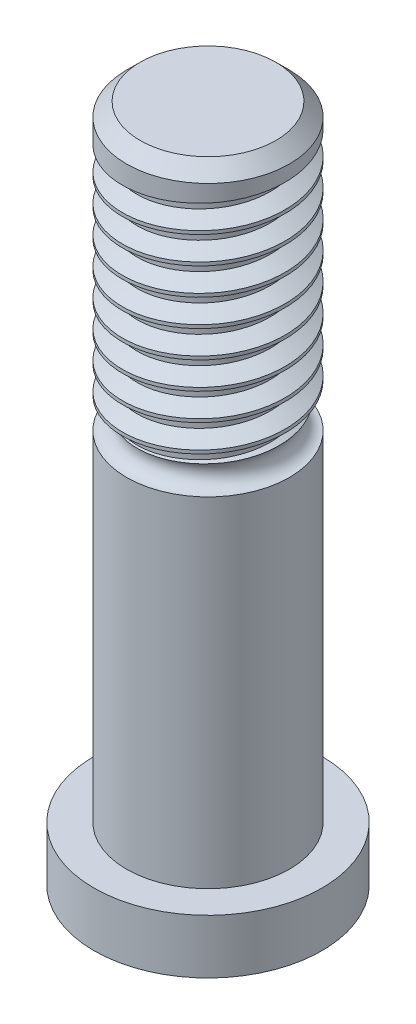
SolidWorks part; units mm, degrees
ref_plane "Front Plane" through (0, 0, 0) normal (0, 0, 1) x (1, 0, 0)
ref_plane "Top Plane" through (0, 0, 0) normal (0, 1, 0) x (1, 0, 0)
ref_plane "Right Plane" through (0, 0, 0) normal (1, 0, 0) x (0, 0, -1)
ref_axis "X-Axis" through (88.99, 0, 0) along (-1, 0, 0)
ref_axis "Y-Axis" through (0, 0, -88.99) along (0, 0, 1)
ref_axis "Z-Axis" through (0, -55, 0) along (0, 1, 0)
sketch "Sketch1" plane through (0, 0, 0) normal (1, 0, 0) x (0, 0, -1)
  line L0 (0, -55) -> (0, 55) construction
  line L1 (0, 12.5) -> (-3, 12.5)
  line L2 (0, 12.5) -> (0, -12.5)
  line L3 (0, -12.5) -> (-3, -12.5)
  line L4 (-3, 12.5) -> (-3, 3)
  line L6 (-3, 2) -> (-3, -10.5)
  line L7 (-3, -12.5) -> (-4.2, -12.5)
  line L9 (-3, -10.5) -> (-4.2, -10.5)
  line L10 (-4.2, -12.5) -> (-4.2, -10.5)
  line L11 (88.99, 0) -> (-88.99, 0) construction
  arc A0 (-3, 2) -> (-3, 3) centre (-3, 2.5) ccw
  point P7 (0, 0)
  dimension "D5" = 0.5
  dimension "D1" = 3
  dimension "D2" = 25
  dimension "D3" = 1.2
  dimension "D4" = 2
  dimension "D6" = 10
revolve "Revolve1" add sketch "Sketch1" angle 360 about axis through (0, -55, 0) along (0, 1, 0)
chamfer "Chamfer1" distance 0.5 angle 45 1 edges at (0, 12.5, -3)
thread "Thread1" pitch 1 method cut profile "Thread Profile1" start angle 0, offset 0, length 0, pitch 1, diameter 6
ref_plane "Plane1" through (-3, 12, 0) normal (0, 0, 1) x (-1, 0, 0)
sketch "Thread Profile1" plane through (-3, 12, 0) normal (0, 0, 1) x (-1, 0, 0)
  line L0 (0, 0) -> (0, 1) construction
  line L11 (0, 0) -> (0, 0.875)
  line L12 (0, 0.875) -> (-0.5413, 0.5625)
  line L13 (-0.5413, 0.5625) -> (-0.5413, 0.3125)
  line L15 (-0.5413, 0.3125) -> (0, 0)
  line L17 (-0.5413, 0.4375) -> (0, 0.4375) construction
  point P2 (0, 0)
  dimension "Pitch" = 1
  dimension "Profile_Angle" = 60
  dimension "Profile_Land" = 0.25
  dimension "Profile_Height" = 0.5413
